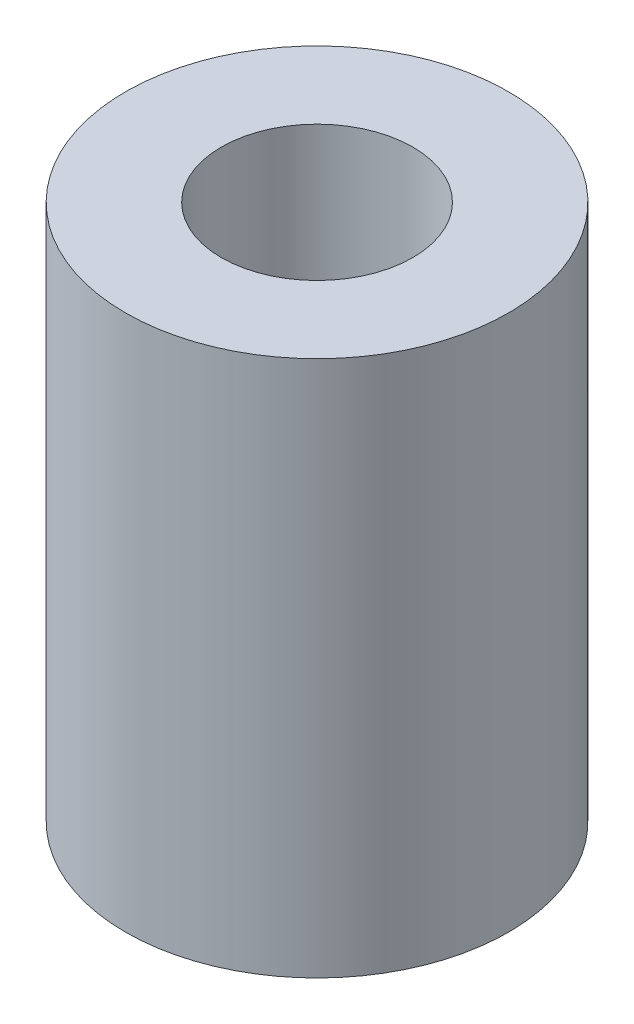
SolidWorks part; units mm, degrees
ref_plane "Front Plane" through (0, 0, 0) normal (0, 0, 1) x (1, 0, 0)
ref_plane "Top Plane" through (0, 0, 0) normal (0, 1, 0) x (1, 0, 0)
ref_plane "Right Plane" through (0, 0, 0) normal (1, 0, 0) x (0, 0, -1)
sketch "Sketch1" plane through (0, 0, 0) normal (0, 1, 0) x (1, 0, 0)
  circle A0 centre (0, 0) radius 2.5
  circle A1 centre (0, 0) radius 1.25
  dimension "D1" = 2.5
  dimension "D2" = 5
extrude "Boss-Extrude1" add sketch "Sketch1" along normal blind 7
